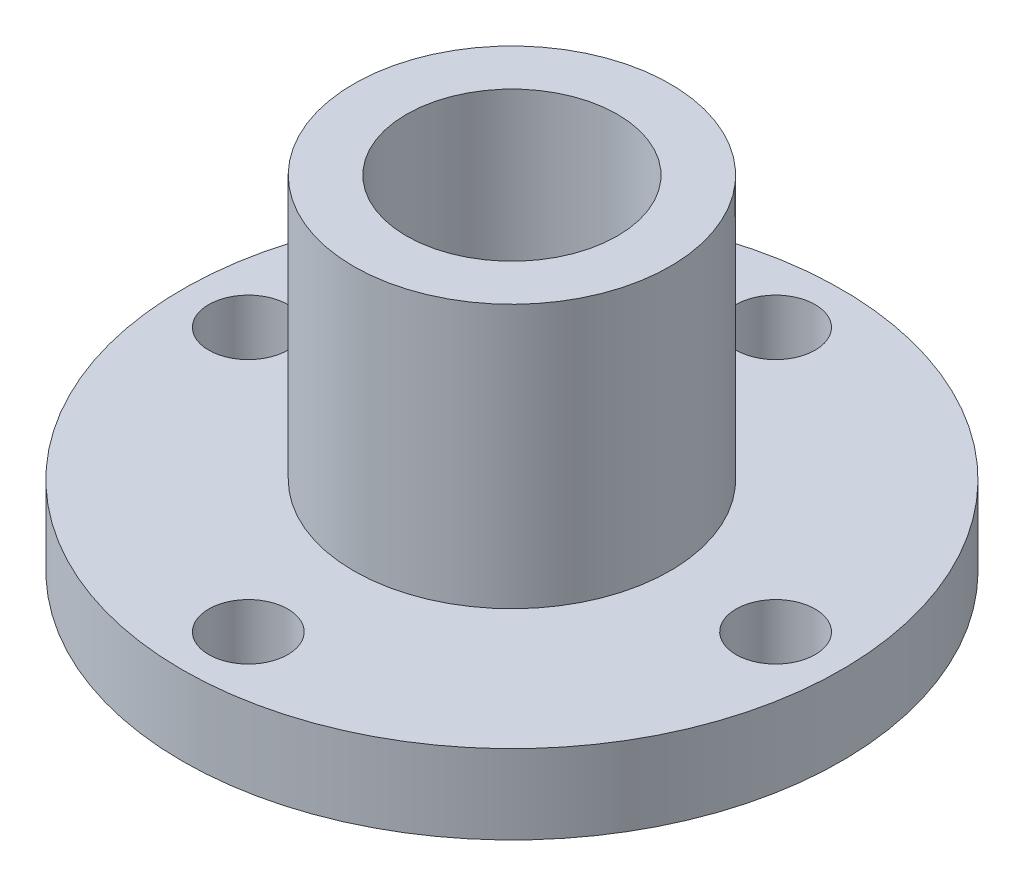
SolidWorks part; units mm, degrees
ref_plane "Front Plane" through (0, 0, 0) normal (0, 0, 1) x (1, 0, 0)
ref_plane "Top Plane" through (0, 0, 0) normal (0, 1, 0) x (1, 0, 0)
ref_plane "Right Plane" through (0, 0, 0) normal (1, 0, 0) x (0, 0, -1)
sketch "Sketch1" plane through (0, 0, 0) normal (0, 1, 0) x (1, 0, 0)
  circle A0 centre (0, 0) radius 12.5
  circle A1 centre (0, 0) radius 6
  circle A2 centre (0, 0) radius 4
  circle A7 centre (0, 0) radius 10 construction
  circle A8 centre (0, 10) radius 1.5
  circle A9 centre (10, 0) radius 1.5
  circle A10 centre (0, -10) radius 1.5
  circle A11 centre (-10, 0) radius 1.5
  point P17 (0, 0)
  dimension "D1" = 8
  dimension "D2" = 2
  dimension "D3" = 25
  dimension "D4" = 20
  dimension "D5" = 3
  dimension "D6" = 4
extrude "Boss-Extrude1" add sketch "Sketch1" along normal blind 3 contours A0 A11 A10 A9 A8 A1 | A1 A2 region at (-12.1464, 0, 0) region at (-5.8303, 0, 0)
extrude "Boss-Extrude2" add sketch "Sketch1<3>" along normal blind 10 from offset 3 contours A1 A2 region at (-5.8303, 0, 0)
sketch "Sketch1<3>" plane through (0, 0, 0) normal (0, 1, 0) x (1, 0, 0) same geometry as "Sketch1"
